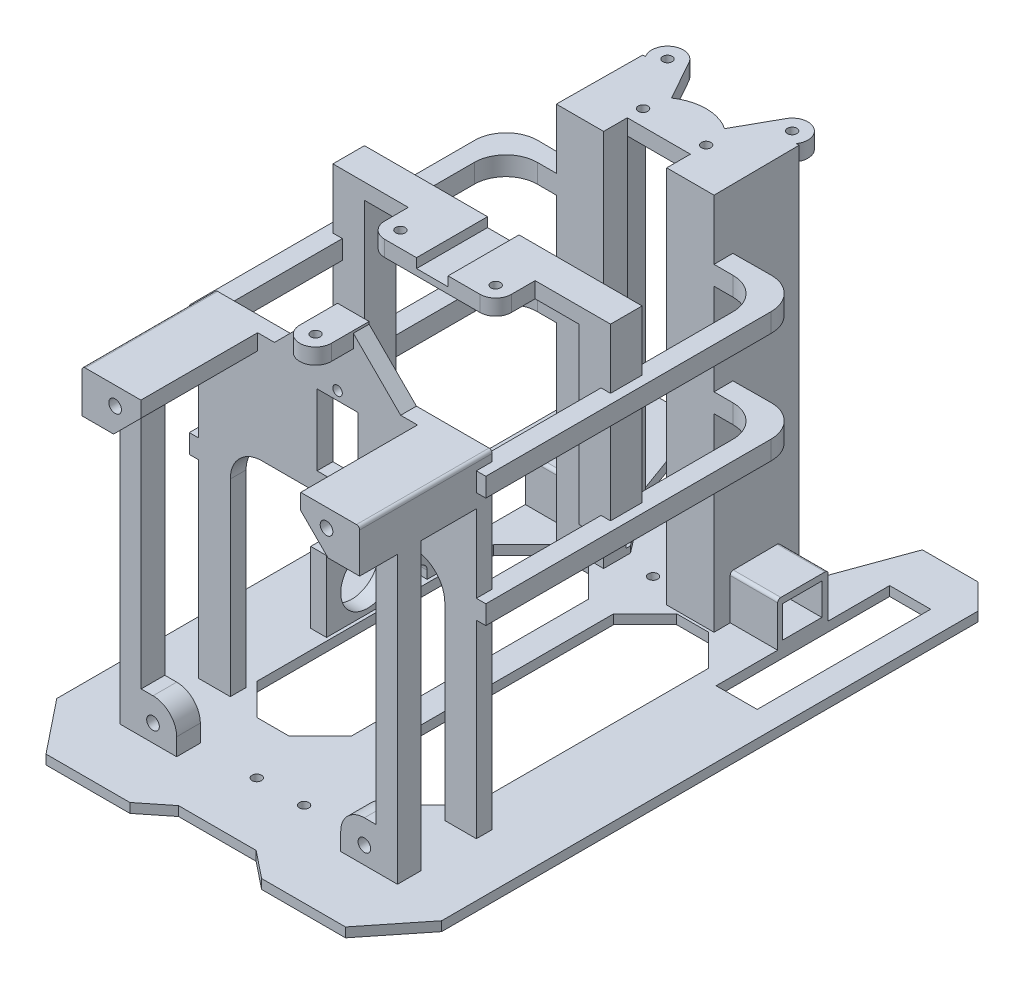
SolidWorks part; units mm, degrees
ref_plane "Front Plane" through (0, 0, 0) normal (0, 0, 1) x (1, 0, 0)
ref_plane "Top Plane" through (0, 0, 0) normal (0, 1, 0) x (1, 0, 0)
ref_plane "Right Plane" through (0, 0, 0) normal (1, 0, 0) x (0, 0, -1)
sketch "Sketch1" plane through (0, 0, 0) normal (1, 0, 0) x (0, 0, -1)
  line L0 (8, 0) -> (8, 13)
  line L1 (6, 2) -> (-6, 2)
  line L2 (6, 2) -> (6, 12)
  line L3 (6, 12) -> (-6, 12)
  line L4 (-6, 2) -> (-6, 12)
  line L5 (6, 2) -> (-6, 12) construction
  line L6 (6, 12) -> (-6, 2) construction
  line L7 (7, 14) -> (-7, 14)
  line L8 (-8, 0) -> (-8, 13)
  line L9 (8, 0) -> (-8, 0)
  line L10 (8, 14) -> (-8, 14) construction
  line L11 (-8, 0) -> (-8, 14) construction
  line L12 (8, 0) -> (8, 14) construction
  arc A0 (-7, 14) -> (-8, 13) centre (-7, 13) ccw
  arc A1 (8, 13) -> (7, 14) centre (7, 13) ccw
  point P0 (0, 7)
  dimension "D4" = 1
  dimension "D1" = 10
  dimension "D2" = 12
  dimension "D3" = 2
extrude "Boss-Extrude1" add sketch "Sketch1" along normal blind 40 and the other way blind 40
sketch "Sketch2" plane through (0, 0, 0) normal (0, 1, 0) x (1, 0, 0)
  line L0 (-40, -27.5) -> (-40, 27.5)
  line L1 (-40, 27.5) -> (-53, 27.5)
  line L2 (-53, 27.5) -> (-53, -27.5)
  line L3 (-53, -27.5) -> (-40, -27.5)
  line L4 (-40, 7) -> (-40, -7) construction
  line L5 (0, 8) -> (0, 0) construction
  line L6 (-40, 8) -> (40, 8) construction
  line L7 (-61, -135.5) -> (-61, 34.5)
  line L8 (-61, 34.5) -> (-53, 42.5)
  line L9 (-53, 42.5) -> (-35.3732, 42.5)
  line L10 (-35.3732, 42.5) -> (-25, 14)
  line L11 (-25, 14) -> (25, 14)
  line L12 (-40, -8) -> (40, -8) construction
  line L13 (0, -145.604) -> (0, -117.4839) construction
  line L14 (20.8801, -152.4563) -> (12.2988, -145.604)
  line L16 (-4, -99) -> (-4, -24)
  line L17 (-4, -24) -> (-14, -14)
  line L18 (-14, -14) -> (-24, -14)
  line L19 (-24, -14) -> (-34, -24)
  line L20 (-34, -24) -> (-34, -99)
  line L21 (-34, -99) -> (-24, -109)
  line L22 (-24, -109) -> (-14, -109)
  line L23 (-14, -109) -> (-4, -99)
  line L24 (-61, -135.5) -> (-47.4603, -152.4563)
  line L25 (-47.4603, -152.4563) -> (-20.8801, -152.4563)
  line L26 (-20.8801, -152.4563) -> (-12.2988, -145.604)
  line L27 (-12.2988, -145.604) -> (12.2988, -145.604)
  line L28 (0, 0) -> (-27.5321, 0) construction
  line L29 (47.4603, -152.4563) -> (20.8801, -152.4563)
  line L30 (61, -135.5) -> (47.4603, -152.4563)
  line L31 (14, -109) -> (4, -99)
  line L32 (24, -109) -> (14, -109)
  line L33 (34, -99) -> (24, -109)
  line L34 (34, -24) -> (34, -99)
  line L35 (24, -14) -> (34, -24)
  line L36 (14, -14) -> (24, -14)
  line L37 (4, -24) -> (14, -14)
  line L38 (4, -99) -> (4, -24)
  line L39 (35.3732, 42.5) -> (25, 14)
  line L40 (53, 42.5) -> (35.3732, 42.5)
  line L41 (61, 34.5) -> (53, 42.5)
  line L42 (61, -135.5) -> (61, 34.5)
  line L43 (53, -27.5) -> (40, -27.5)
  line L44 (53, 27.5) -> (53, -27.5)
  line L45 (40, 27.5) -> (53, 27.5)
  line L46 (40, -27.5) -> (40, 27.5)
  circle A0 centre (-7.5, -125.604) radius 1.5
  circle A1 centre (7.5, -125.604) radius 1.5
  circle A2 centre (0, -7.5) radius 1.5
  circle A3 centre (0, 7.5) radius 1.5
  point P47 (0, 14)
  point P48 (0, -145.604)
  dimension "D20" = 3
  dimension "D23" = 3
  dimension "D1" = 13
  dimension "D2" = 55
  dimension "D3" = 15
  dimension "D4" = 45
  dimension "D5" = 70
  dimension "D6" = 15
  dimension "D7" = 8
  dimension "D8" = 6
  dimension "D9" = 8
  dimension "D10" = 45
  dimension "D11" = 45
  dimension "D12" = 45
  dimension "D13" = 45
  dimension "D14" = 6
  dimension "D15" = 75
  dimension "D16" = 30
  dimension "D17" = 10
  dimension "D18" = 6
  dimension "D19" = 170
  dimension "D21" = 7.5
  dimension "D22" = 20
  dimension "D24" = 7.5
extrude "Boss-Extrude2" add sketch "Sketch2" against normal blind 3
ref_plane "Plane1" through (0, 120, 0) normal (0, 1, 0) x (1, 0, 0)
sketch "Sketch5" plane through (0, 120, 0) normal (0, 1, 0) x (1, 0, 0)
  line L0 (0, 12.3373) -> (0, -2.476) construction
  line L6 (-2.5, -2.476) -> (2.5, -2.476)
  line L7 (2.5, -72.7063) -> (2.5, -2.476)
  line L8 (-2.5, -72.7063) -> (-2.5, -2.476)
  line L9 (6, -100.976) -> (-6, -100.976)
  line L10 (-6, -100.976) -> (-6, -77.476)
  line L11 (6, -77.476) -> (6, -100.976)
  line L14 (0, -100.976) -> (0, -2.476) construction
  line L48 (-22.6, -113.476) -> (-6, -113.476)
  line L49 (-1, -118.476) -> (1, -118.476)
  line L50 (6, -113.476) -> (22.6, -113.476)
  line L51 (22.6, -113.476) -> (22.6, -64.976)
  line L52 (22.6, -64.976) -> (13.5, -64.976)
  line L53 (8.5, -59.976) -> (8.5, -3.4717)
  line L54 (8.5, -3.4717) -> (23.4538, -7.46)
  line L55 (26.5462, 4.1347) -> (22.25, 5.2805)
  line L56 (22.25, 5.2805) -> (22.25, 19.3373)
  line L57 (22.25, 19.3373) -> (9.25, 19.3373)
  line L58 (9.25, 19.3373) -> (9.25, 16.3373)
  line L59 (9.25, 16.3373) -> (11.25, 16.3373)
  line L60 (11.25, 16.3373) -> (11.25, 12.3373)
  line L61 (11.25, 12.3373) -> (-11.25, 12.3373)
  line L62 (-11.25, 12.3373) -> (-11.25, 16.3373)
  line L63 (-11.25, 16.3373) -> (-9.25, 16.3373)
  line L64 (-9.25, 16.3373) -> (-9.25, 19.3373)
  line L65 (-9.25, 19.3373) -> (-22.25, 19.3373)
  line L66 (-22.25, 19.3373) -> (-22.25, 5.2805)
  line L67 (-22.25, 5.2805) -> (-26.5462, 4.1347)
  line L68 (-23.4538, -7.46) -> (-8.5, -3.4717)
  line L69 (-8.5, -3.4717) -> (-8.5, -59.976)
  line L70 (-13.5, -64.976) -> (-22.6, -64.976)
  line L71 (-22.6, -64.976) -> (-22.6, -113.476)
  arc A12 (-6, -113.476) -> (-1, -118.476) centre (-1, -113.476) ccw
  arc A13 (1, -118.476) -> (6, -113.476) centre (1, -113.476) ccw
  arc A14 (8.5, -59.976) -> (13.5, -64.976) centre (13.5, -59.976) ccw
  arc A15 (23.4538, -7.46) -> (26.5462, 4.1347) centre (25, -1.6627) ccw
  arc A16 (-26.5462, 4.1347) -> (-23.4538, -7.46) centre (-25, -1.6627) ccw
  arc A17 (-13.5, -64.976) -> (-8.5, -59.976) centre (-13.5, -59.976) ccw
  arc A23 (2.5, -72.7063) -> (6, -77.476) centre (7.5, -72.7063) ccw
  arc A24 (-6, -77.476) -> (-2.5, -72.7063) centre (-7.5, -72.7063) ccw
  circle A25 centre (0, -114.476) radius 1.5
  circle A26 centre (-15.1, -72.476) radius 1.5
  circle A27 centre (15.1, -72.476) radius 1.5
  circle A28 centre (19.75, 16.8373) radius 1.5
  circle A29 centre (-19.75, 16.8373) radius 1.5
  circle A30 centre (25, -1.6627) radius 3
  circle A31 centre (10, -0.6627) radius 1.5
  circle A32 centre (-10, -0.6627) radius 1.5
  circle A33 centre (-25, -1.6627) radius 3
  dimension "D1" = 13
  dimension "D2" = 10
ref_plane "Plane2" through (0, 0, 132.5) normal (0, 0, 1) x (1, 0, 0)
sketch "Sketch8" plane through (0, 0, 132.5) normal (0, 0, 1) x (1, 0, 0)
  line L8 (-12, 5.1605) -> (-10, 5.1605)
  line L9 (-10, 5.1605) -> (-10, 15.1605)
  line L10 (-10, 15.1605) -> (-12, 15.1605)
  line L11 (-12, 15.1605) -> (-12, 5.1605)
  line L16 (16, 15.1605) -> (14, 15.1605)
  line L17 (14, 15.1605) -> (14, 5.1605)
  line L18 (14, 5.1605) -> (16, 5.1605)
  line L19 (16, 5.1605) -> (16, 15.1605)
  line L20 (-37, 2) -> (37, 2)
  line L21 (37, 2) -> (37, 102)
  line L22 (-37, 102) -> (-37, 2)
  line L23 (37, 102) -> (-37, 102)
  circle A6 centre (18, 98.5) radius 2
  circle A7 centre (33.5, 98.5) radius 2
  circle A8 centre (-15, 97) radius 2
  circle A9 centre (-33.5, 98.5) radius 2
  circle A10 centre (-33.5, 5.5) radius 2
  circle A11 centre (33.5, 5.5) radius 2
ref_plane "Plane3" through (0, 0, 102.5) normal (0, 0, -1) x (-1, 0, 0)
sketch "Sketch9" plane through (0, 0, 102.5) normal (0, 0, -1) x (-1, 0, 0)
  line L0 (0, 101) -> (0, 73) construction
  line L1 (-37, 102) -> (37, 102) construction
  line L2 (6.5, 75.75) -> (-6.5, 75.75)
  line L3 (6.5, 75.75) -> (6.5, 98.25)
  line L4 (6.5, 98.25) -> (-6.5, 98.25)
  line L5 (-6.5, 75.75) -> (-6.5, 98.25)
  line L6 (6.5, 75.75) -> (-6.5, 98.25) construction
  line L7 (6.5, 98.25) -> (-6.5, 75.75) construction
  circle A0 centre (0, 101) radius 1.5
  circle A1 centre (0, 73) radius 1.5
  point P3 (0, 87)
  dimension "D1" = 3
  dimension "D2" = 3
  dimension "D3" = 13
  dimension "D4" = 22.5
  dimension "D5" = 28
  dimension "D6" = 14
  dimension "D7" = 15
sketch "Sketch10" plane through (0, 0, 102.5) normal (0, 0, -1) x (-1, 0, 0)
  line L0 (-6.5, 75.75) -> (-6.5, 98.25) construction
  line L1 (6.5, 75.75) -> (-6.5, 75.75) construction
  line L2 (6.5, 75.75) -> (6.5, 98.25) construction
  line L3 (6.5, 98.25) -> (-6.5, 98.25) construction
  line L4 (-6.5, 75.75) -> (-6.5, 98.25)
  line L5 (6.5, 75.75) -> (-6.5, 75.75)
  line L6 (6.5, 75.75) -> (6.5, 98.25)
  line L7 (6.5, 98.25) -> (-6.5, 98.25)
  line L8 (34, 0) -> (34, 59.75)
  line L9 (47.4603, 0) -> (20.8801, 0) construction
  line L10 (24, 69.75) -> (-24, 69.75)
  line L11 (-34, 59.75) -> (-34, 0)
  line L12 (-20.8801, 0) -> (-47.4603, 0) construction
  line L13 (-34, 0) -> (-44, 0)
  line L14 (-47.4603, 0) -> (-61, 0) construction
  line L15 (-44, 0) -> (-44, 103.25)
  line L16 (-43, 104.25) -> (43, 104.25)
  line L17 (44, 103.25) -> (44, 0)
  line L18 (61, 0) -> (47.4603, 0) construction
  line L19 (44, 0) -> (34, 0)
  line L21 (0, 101) -> (0, 73) construction
  circle A0 centre (0, 73) radius 1.5 construction
  circle A1 centre (0, 101) radius 1.5 construction
  circle A2 centre (0, 73) radius 1.5
  circle A3 centre (0, 101) radius 1.5
  arc A4 (-44, 103.25) -> (-43, 104.25) centre (-43, 103.25) cw
  arc A5 (43, 104.25) -> (44, 103.25) centre (43, 103.25) cw
  arc A6 (-24, 69.75) -> (-34, 59.75) centre (-24, 59.75) ccw
  arc A7 (34, 59.75) -> (24, 69.75) centre (24, 59.75) ccw
  dimension "D5" = 1
  dimension "D6" = 10
  dimension "D1" = 6
  dimension "D2" = 6
  dimension "D3" = 10
  dimension "D4" = 0
extrude "Boss-Extrude3" add sketch "Sketch10" against normal blind 5
sketch "Sketch11" plane through (0, 120, 0) normal (0, 1, 0) x (1, 0, 0)
  line L0 (10, -0.6627) -> (19.75, 16.8373) construction
  line L1 (5.6322, 1.7708) -> (15.3822, 19.2708)
  line L2 (14.3678, -3.0962) -> (24.1178, 14.4038)
  line L3 (-19.75, 16.8373) -> (-10, -0.6627) construction
  line L4 (-15.3822, 19.2708) -> (-5.6322, 1.7708)
  line L5 (-24.1178, 14.4038) -> (-14.3678, -3.0962)
  line L6 (10, -5.6627) -> (-10, -5.6627)
  line L7 (15.1, -72.476) -> (-15.1, -72.476) construction
  line L8 (15.1, -77.476) -> (-15.1, -77.476)
  line L10 (-20.1, -72.476) -> (-20.1, -64.976)
  line L11 (-20.1, -64.976) -> (-44, -64.976)
  line L12 (-44, -64.976) -> (-44, -54.976)
  line L13 (-44, -54.976) -> (44, -54.976)
  line L14 (44, -54.976) -> (44, -64.976)
  line L15 (44, -64.976) -> (20.1, -64.976)
  line L16 (20.1, -64.976) -> (20.1, -72.476)
  line L17 (0, -114.476) -> (0, -107.5) construction
  line L18 (-43, -107.5) -> (43, -107.5) construction
  line L19 (-5, -114.476) -> (-5, -107.5)
  line L20 (5, -114.476) -> (5, -107.5)
  line L21 (5, -107.5) -> (5, -102.5)
  line L22 (-6.5, -102.5) -> (6.5, -102.5) construction
  line L23 (5, -102.5) -> (-5, -102.5)
  line L24 (-6.5, -102.5) -> (6.5, -102.5) construction
  line L25 (-5, -102.5) -> (-5, -107.5)
  line L26 (-40, -7) -> (40, -7) construction
  line L27 (-34, -24) -> (-34, -99) construction
  line L28 (10, -5.6627) -> (10, -13.1627)
  line L29 (10, -13.1627) -> (25, -13.1627)
  line L30 (25, -13.1627) -> (24.7738, 14)
  line L31 (25, 14) -> (-25, 14) construction
  line L32 (24.7738, 14) -> (23.8929, 14)
  line L33 (0, -5.6627) -> (0, -27.4644) construction
  line L34 (-24.7738, 14) -> (-23.8929, 14)
  line L35 (-25, -13.1627) -> (-24.7738, 14)
  line L36 (-10, -13.1627) -> (-25, -13.1627)
  line L37 (-10, -5.6627) -> (-10, -13.1627)
  circle A0 centre (0, -114.476) radius 1.5 construction
  circle A1 centre (-15.1, -72.476) radius 1.5 construction
  circle A2 centre (15.1, -72.476) radius 1.5 construction
  circle A3 centre (10, -0.6627) radius 1.5 construction
  circle A4 centre (-10, -0.6627) radius 1.5 construction
  circle A5 centre (-19.75, 16.8373) radius 1.5 construction
  circle A6 centre (19.75, 16.8373) radius 1.5 construction
  circle A7 centre (0, -114.476) radius 1.5
  circle A8 centre (-15.1, -72.476) radius 1.5
  circle A9 centre (15.1, -72.476) radius 1.5
  circle A10 centre (10, -0.6627) radius 1.5
  circle A11 centre (-10, -0.6627) radius 1.5
  circle A12 centre (-19.75, 16.8373) radius 1.5
  circle A13 centre (19.75, 16.8373) radius 1.5
  arc A14 (5.6322, 1.7708) -> (14.3678, -3.0962) centre (10, -0.6627) ccw
  arc A15 (24.1178, 14.4038) -> (15.3822, 19.2708) centre (19.75, 16.8373) ccw
  arc A16 (-15.3822, 19.2708) -> (-24.1178, 14.4038) centre (-19.75, 16.8373) ccw
  arc A17 (-14.3678, -3.0962) -> (-5.6322, 1.7708) centre (-10, -0.6627) ccw
  arc A18 (-8.4105, 6.7576) -> (8.4105, 6.7576) centre (0, -5.6627) cw
  arc A19 (15.1, -77.476) -> (20.1, -72.476) centre (15.1, -72.476) ccw
  arc A20 (-20.1, -72.476) -> (-15.1, -77.476) centre (-15.1, -72.476) ccw
  arc A21 (-5, -114.476) -> (5, -114.476) centre (0, -114.476) ccw
  point P21 (14.875, 8.0873)
  point P26 (-14.875, 8.0873)
  point P36 (0, -72.476)
  point P39 (0, -110.988)
  dimension "D1" = 5
  dimension "D2" = 5
  dimension "D3" = 15
  dimension "D4" = 5
  dimension "D8" = 5
  dimension "D5" = 10
  dimension "D6" = 10
  dimension "D7" = 7.5
  dimension "D9" = 15
  dimension "D10" = 7.5
extrude "Boss-Extrude4" add sketch "Sketch11" against normal blind 5 separate body contours L10 A20 L8 A19 L16 L15 L14 L13 L12 L11 A8 A9 | L19 A21 L20 L21 L23 L25 A7 | A17 L4 A16 L5 A11 A12 | A18 L4 A17 L6 A14 L1 | L2 A15 L1 A14 L6 A10 A13 | A14 L28 L29 L30 L32 L2 | A17 L5 L34 L35 L36 L37 region at (0, 120, -1.8735) region at (14.875, 120, -8.0873) region at (19.2343, 120, 3.7226) region at (-14.875, 120, -8.0873) region at (-19.2343, 120, 3.7226) region at (0, 120, 63.8803) region at (0, 120, 110.3053)
sketch "Sketch12" plane through (0, 0, 54.976) normal (0, 0, -1) x (-1, 0, 0)
  line L0 (44, 120) -> (-44, 120) construction
  line L1 (-5, 120) -> (5, 120)
  line L2 (-5, 120) -> (-5, 117)
  line L3 (-5, 117) -> (5, 117)
  line L4 (5, 120) -> (5, 117)
  line L5 (0, 115) -> (0, 120) construction
  line L6 (44, 115) -> (-44, 115) construction
  point P11 (0, 120)
  dimension "D1" = 3
  dimension "D2" = 10
extrude "Cut-Extrude1" cut sketch "Sketch12" against normal up to surface (22.5 mm away) up to face at (0, 117.5, 77.476)
sketch "Sketch13" plane through (0, 115, 0) normal (0, -1, 0) x (1, 0, 0)
  line L2 (0, 0) -> (0, 54.976) construction
  line L3 (-44, 54.976) -> (44, 54.976) construction
  line L5 (44, 64.976) -> (34, 64.976)
  line L6 (44, 64.976) -> (44, 54.976)
  line L7 (44, 54.976) -> (34, 54.976)
  line L8 (34, 64.976) -> (34, 54.976)
  line L9 (-44, 54.976) -> (-34, 54.976)
  line L10 (-34, 64.976) -> (-34, 54.976)
  line L11 (-44, 64.976) -> (-34, 64.976)
  line L12 (-44, 64.976) -> (-44, 54.976)
  line L14 (-10, 5.6627) -> (-23.8929, -14)
  line L15 (-10, 5.6627) -> (-10, 13.1627)
  line L16 (-10, 13.1627) -> (-25, 13.1627)
  line L17 (-25, 13.1627) -> (-24.7738, -14)
  line L18 (-24.7738, -14) -> (-23.8929, -14)
  line L19 (24.7738, -14) -> (23.8929, -14)
  line L20 (25, 13.1627) -> (24.7738, -14)
  line L21 (10, 13.1627) -> (25, 13.1627)
  line L22 (10, 5.6627) -> (10, 13.1627)
  line L23 (10, 5.6627) -> (23.8929, -14)
  dimension "D2" = 10
extrude "Boss-Extrude5" add sketch "Sketch13" along normal up to surface (115 mm away) up to face at (19, 0, 61.5)
ref_plane "Plane4" through (-35, 0, 0) normal (1, 0, 0) x (0, 0, -1)
sketch "Sketch14" plane through (-35, 0, 0) normal (1, 0, 0) x (0, 0, -1)
  line L8 (-55, 20) -> (-45, 20)
  line L9 (-45, 20) -> (-45, 27.5)
  line L10 (-45, 27.5) -> (-55, 27.5)
  line L11 (-55, 27.5) -> (-55, 20)
  line L12 (-72.5, 20) -> (-72.5, 0)
  line L13 (-72.5, 0) -> (-27.5, 0)
  line L14 (-27.5, 0) -> (-27.5, 20)
  line L15 (-27.5, 20) -> (-72.5, 20)
  line L18 (-46.5, 4.9) -> (-53.5, 4.9)
  line L19 (-53.5, 0.1) -> (-46.5, 0.1)
  circle A4 centre (-37, 10) radius 8.5
  arc A5 (-46.5, 0.1) -> (-46.5, 4.9) centre (-46.5, 2.5) ccw
  arc A6 (-53.5, 4.9) -> (-53.5, 0.1) centre (-53.5, 2.5) ccw
  circle A7 centre (-63, 10) radius 8.5
sketch "Sketch15" plane through (0, 0, 132.5) normal (0, 0, 1) x (1, 0, 0)
  line L0 (-33.5, 5.5) -> (-33.5, 0) construction
  line L1 (-47.4603, 0) -> (-20.8801, 0) construction
  line L2 (-26, 5.5) -> (-26, 0)
  line L4 (-41, 0) -> (-26, 0)
  line L5 (-33.5, 13) -> (-37.25, 13)
  line L6 (33.5, 5.5) -> (33.5, 0) construction
  line L7 (44, 0) -> (44, 100)
  line L11 (-37.25, 13) -> (-37.25, 100)
  line L12 (37.25, 100) -> (44, 100)
  line L13 (41, 0) -> (44, 0)
  line L14 (0, 0) -> (0, 31.7264) construction
  line L15 (-41, 0) -> (-44, 0)
  line L17 (-37.25, 100) -> (-44, 100)
  line L18 (-44, 0) -> (-44, 100)
  line L19 (37.25, 13) -> (37.25, 100)
  line L20 (33.5, 13) -> (37.25, 13)
  line L21 (41, 0) -> (26, 0)
  line L22 (26, 5.5) -> (26, 0)
  line L23 (-61, 0) -> (-47.4603, 0) construction
  arc A0 (26, 5.5) -> (33.5, 13) centre (33.5, 5.5) cw
  circle A1 centre (-33.5, 5.5) radius 2 construction
  circle A3 centre (-33.5, 5.5) radius 2
  arc A4 (-26, 5.5) -> (-33.5, 13) centre (-33.5, 5.5) ccw
  circle A5 centre (33.5, 5.5) radius 2
  point P6 (-33.5, 2.75)
  point P29 (33.5, 2.75)
  dimension "D1" = 7.5
  dimension "D2" = 6.75
  dimension "D3" = 5.5
  dimension "D4" = 100
  dimension "D5" = 3.75
extrude "Boss-Extrude6" add sketch "Sketch15" against normal blind 7.5 contours A3 L4 L2 A4 | A4 L5 | L12 L19 | L12 region at (-39.2813, 43.3019, 132.5) region at (39.2813, 43.3019, 132.5)
sketch "Sketch17" plane through (0, 0, 0) normal (0, 1, 0) x (1, 0, 0)
  line L0 (-19.6535, 8) -> (19.6535, 8) construction
  line L1 (-19.6535, 8) -> (19.6535, 8)
  line L2 (-10, -8) -> (10, -8) construction
  line L3 (-10, -8) -> (10, -8)
  line L4 (-10, -8) -> (-10, -4.6627)
  line L5 (-10, -5.6627) -> (-10, -13.1627) construction
  line L6 (-10, -5.6627) -> (-10, -7) construction
  line L7 (-10, -4.6627) -> (-19.6535, 8)
  line L8 (10, -8) -> (10, -5.6627)
  line L9 (10, -5.6627) -> (19.6535, 8)
extrude "Cut-Extrude3" cut sketch "Sketch17" along normal up to surface (14 mm away) up to face at (0, 14, 1.8876)
sketch "Sketch18" plane through (-24.8887, 0, -0.2073) normal (-1, 0, -0.0083) x (-0.0083, 0, 1)
  line L4 (-5.7929, 2) -> (6.2075, 2)
  line L5 (6.2075, 2) -> (6.2075, 12)
  line L6 (6.2075, 12) -> (-5.7929, 12)
  line L7 (-5.7929, 12) -> (-5.7929, 2)
  line L8 (-5.7929, 2) -> (6.2075, 2)
  line L9 (6.2075, 2) -> (6.2075, 12)
  line L10 (6.2075, 12) -> (-5.7929, 12)
  line L11 (-5.7929, 12) -> (-5.7929, 2)
  dimension "D1" = 0
extrude "Cut-Extrude4" cut sketch "Sketch18" against normal through all both and the other way through all
ref_plane "Plane5" through (0, 60, 0) normal (0, 1, 0) x (1, 0, 0)
sketch "Sketch19" plane through (0, 60, 0) normal (0, 1, 0) x (1, 0, 0)
  line L0 (0, -114.476) -> (0, -7.5) construction
  line L1 (41, -107.5) -> (47, -107.5)
  line L2 (43, -107.5) -> (44, -107.5) construction
  line L3 (47, -107.5) -> (47, -17.0627)
  line L4 (36.9167, -7.063) -> (24.95, -7.1627)
  line L5 (24.8321, 7) -> (24.9487, -7) construction
  line L6 (24.95, -7.1627) -> (25, -13.1627)
  line L7 (25, -13.1627) -> (31, -13.1627)
  line L8 (41, -23.1627) -> (41, -107.5)
  line L9 (44, -107.5) -> (44, -102.5) construction
  line L10 (-41, -23.1627) -> (-41, -107.5)
  line L11 (-25, -13.1627) -> (-31, -13.1627)
  line L12 (-24.95, -7.1627) -> (-25, -13.1627)
  line L13 (-36.9167, -7.063) -> (-24.95, -7.1627)
  line L14 (-47, -107.5) -> (-47, -17.0627)
  line L15 (-41, -107.5) -> (-47, -107.5)
  arc A0 (31, -13.1627) -> (41, -23.1627) centre (31, -23.1627) cw
  arc A1 (47, -17.0627) -> (36.9167, -7.063) centre (37, -17.0627) ccw
  arc A2 (-47, -17.0627) -> (-36.9167, -7.063) centre (-37, -17.0627) cw
  arc A3 (-31, -13.1627) -> (-41, -23.1627) centre (-31, -23.1627) ccw
  dimension "D4" = 10
  dimension "D5" = 10
  dimension "D1" = 3
  dimension "D2" = 3
  dimension "D3" = 6
extrude "Boss-Extrude7" add sketch "Sketch19" along normal blind 6
sketch "Sketch20" plane through (0, 0, 0) normal (1, 0, 0) x (0, 0, -1)
  line L0 (67.1, 60) -> (-67.1, 60) construction
  line L1 (-80.9169, 60) -> (-41.3493, 60)
  line L2 (-80.9169, 60) -> (-80.9169, 0)
  line L3 (-80.9169, 0) -> (-41.3493, 0)
  line L4 (-41.3493, 60) -> (-41.3493, 0)
  line L5 (-72.5, 0) -> (-27.5, 0) construction
extrude "Cut-Extrude5" cut sketch "Sketch20" against normal through all both and the other way through all
sketch "Sketch21" plane through (0, 0, 132.5) normal (0, 0, 1) x (1, 0, 0)
  line L0 (43, 104.25) -> (25.3303, 104.25)
  line L1 (-43, 104.25) -> (43, 104.25) construction
  line L2 (25.3303, 104.25) -> (25.3303, 99.25)
  line L3 (25.3303, 99.25) -> (34, 90.5803)
  line L4 (34, 90.5803) -> (44, 90.5803)
  line L5 (44, 103.25) -> (44, 66) construction
  line L6 (44, 90.5803) -> (44, 103.25)
  line L7 (0, 101) -> (0, 73) construction
  line L8 (-34, 90.5803) -> (-44, 90.5803)
  line L9 (-25.3303, 99.25) -> (-34, 90.5803)
  line L10 (-25.3303, 104.25) -> (-25.3303, 99.25)
  line L11 (-43, 104.25) -> (-25.3303, 104.25)
  line L12 (-44, 90.5803) -> (-44, 103.25)
  arc A0 (44, 103.25) -> (43, 104.25) centre (43, 103.25) ccw construction
  arc A1 (44, 103.25) -> (43, 104.25) centre (43, 103.25) ccw
  circle A2 centre (33.5, 98.5) radius 2 construction
  circle A3 centre (33.5, 98.5) radius 2
  circle A4 centre (-33.5, 98.5) radius 2
  arc A5 (-44, 103.25) -> (-43, 104.25) centre (-43, 103.25) cw
  dimension "D1" = 45
  dimension "D2" = 5
  dimension "D3" = 10
extrude "Boss-Extrude8" add sketch "Sketch21" against normal up to surface (25 mm away) and the other way blind 12 up to face at (0, 59.1278, 107.5)
sketch "Sketch23" plane through (0, 104.25, 0) normal (0, 1, 0) x (1, 0, 0)
  line L0 (5, -114.476) -> (5, -102.5) construction
  line L1 (-5, -102.5) -> (5, -102.5)
  line L2 (-5, -102.5) -> (-5, -107.5)
  line L3 (-5, -107.5) -> (5, -107.5)
  line L4 (5, -102.5) -> (5, -107.5)
  line L5 (-25.3303, -107.5) -> (25.3303, -107.5) construction
extrude "Boss-Extrude9" add sketch "Sketch23" along normal up to surface (10.75 mm away) up to face at (0, 115, 115.976)
chamfer "Chamfer1" distance 15 angle 45 2 edges at (-5, 104.25, 105) (5, 104.25, 105)
pattern_linear "LPattern2" count 2 spacing 35 along (0, 1, 0) of "Boss-Extrude7"
sketch "Sketch24" plane through (-35, 0, 0) normal (1, 0, 0) x (0, 0, -1)
  line L0 (-44.1, 2.5) -> (-44.1, 0)
  line L1 (-72.5, 0) -> (-27.5, 0) construction
  line L2 (-55.9, 2.5) -> (-55.9, 0)
  line L3 (-55.9, 0) -> (-76, 0)
  line L4 (34.5, 0) -> (-135.5, 0) construction
  line L5 (-76, 0) -> (-76, 22.5)
  line L6 (-76, 22.5) -> (-24, 22.5)
  line L7 (-24, 22.5) -> (-24, 0)
  line L8 (-24, 0) -> (-44.1, 0)
  line L9 (-46.5, 4.9) -> (-53.5, 4.9) construction
  line L10 (-46.5, 4.9) -> (-53.5, 4.9)
  circle A0 centre (-37, 10) radius 8.5 construction
  circle A1 centre (-63, 10) radius 8.5 construction
  circle A2 centre (-37, 10) radius 8.5
  circle A3 centre (-63, 10) radius 8.5
  arc A4 (-46.5, 0.1) -> (-46.5, 4.9) centre (-46.5, 2.5) ccw construction
  arc A5 (-53.5, 4.9) -> (-53.5, 0.1) centre (-53.5, 2.5) ccw construction
  arc A6 (-53.5, 4.9) -> (-55.9, 2.5) centre (-53.5, 2.5) ccw
  arc A7 (-44.1, 2.5) -> (-46.5, 4.9) centre (-46.5, 2.5) ccw
  dimension "D1" = 22.5
  dimension "D2" = 22.5
  dimension "D3" = 22.5
extrude "Boss-Extrude10" add sketch "Sketch24" against normal blind 5
chamfer "Chamfer2" distance 3 angle 45 2 edges at (-41, 60, 83.738) (41, 60, 83.738)
